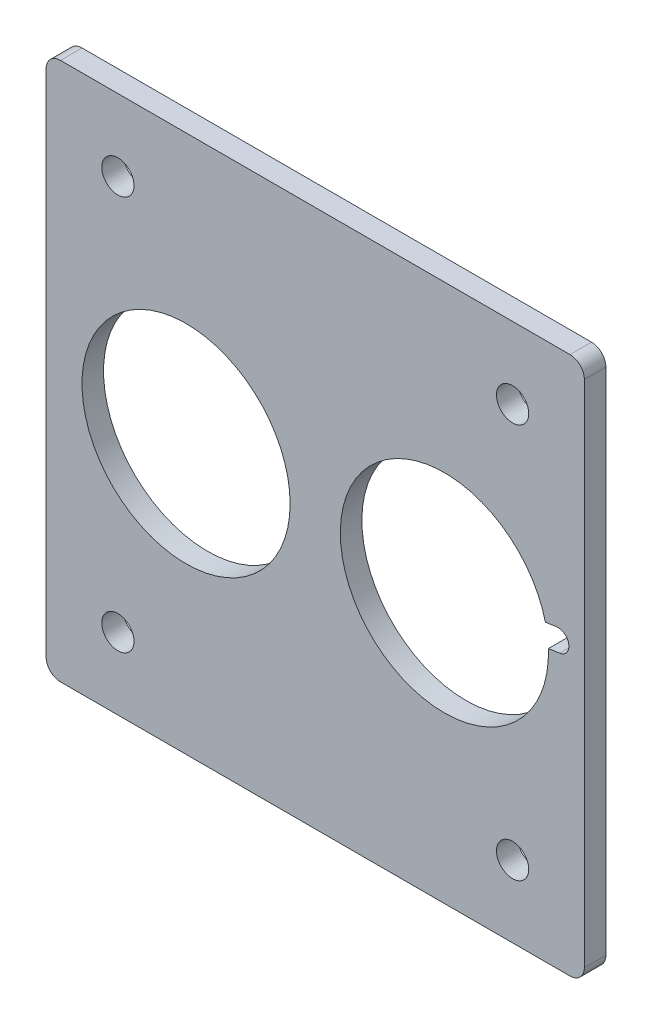
SolidWorks part; units mm, degrees
material "1.5714 (16NiCr4)"
ref_plane "Ebene vorne" through (0, 0, 0) normal (0, 0, 1) x (1, 0, 0)
ref_plane "Ebene oben" through (0, 0, 0) normal (0, 1, 0) x (1, 0, 0)
ref_plane "Ebene rechts" through (0, 0, 0) normal (1, 0, 0) x (0, 0, -1)
sketch "Skizze1" plane through (0, 0, 0) normal (0, 0, 1) x (1, 0, 0)
  line L1 (-37.5, -37.5) -> (37.5, -37.5)
  line L2 (-37.5, -37.5) -> (-37.5, 37.5)
  line L3 (-37.5, 37.5) -> (37.5, 37.5)
  line L4 (37.5, -37.5) -> (37.5, 37.5)
  line L5 (-37.5, -37.5) -> (37.5, 37.5) construction
  line L6 (-37.5, 37.5) -> (37.5, -37.5) construction
  point P0 (0, 0)
  dimension "D1" = 75
  dimension "D2" = 75
extrude "Aufsatz-Linear austragen1" add sketch "Skizze1" along normal blind 3
sketch "Skizze2" plane through (0, 0, 3) normal (0, 0, 1) x (1, 0, 0)
  line L0 (-18, 0) -> (18, 0) construction
  line L1 (18, 0) -> (37.5, 0) construction
  line L2 (37.5, -37.5) -> (37.5, 37.5) construction
  line L3 (-18, 0) -> (-37.5, 0) construction
  line L4 (-37.5, 37.5) -> (-37.5, -37.5) construction
  circle A0 centre (-18, 0) radius 14.5
  circle A1 centre (18, 0) radius 14.5
  dimension "D1" = 29
  dimension "D2" = 36
extrude "Schnitt-Linear austragen1" cut sketch "Skizze2" against normal through all
fillet "Verrundung1" radius 2 4 edges at (-37.5, -37.5, 1.5) (-37.5, 37.5, 1.5) (37.5, -37.5, 1.5) (37.5, 37.5, 1.5)
hole_wizard "Durchgangsloch für M41" positions "Skizze4" profile "Skizze5" hole size "M4" standard "ANSI Metrisch" end condition through all
sketch "Skizze4" plane through (0, 0, 3) normal (0, 0, 1) x (1, 0, 0)
  line L0 (-37.5, 27.5) -> (-27.5, 27.5) construction
  line L1 (-37.5, 35.5) -> (-37.5, -35.5) construction
  line L2 (-27.5, 27.5) -> (27.5, 27.5) construction
  line L3 (27.5, 27.5) -> (37.5, 27.5) construction
  line L4 (37.5, -35.5) -> (37.5, 35.5) construction
  line L5 (35.5, 37.5) -> (-35.5, 37.5) construction
  point P2 (-27.5, 27.5)
  point P6 (27.5, 27.5)
  dimension "D1" = 10
  dimension "D2" = 10
sketch "Skizze5" plane through (27.5, 27.5, 3) normal (1, 0, 0) x (0, -1, 0)
  line L0 (0, 0) -> (0, 3)
  line L1 (0, 3) -> (2.25, 3)
  line L2 (2.25, 3) -> (2.25, 0)
  line L5 (2.25, 0) -> (0, 0)
  line L11 (0, -6.35) -> (0, 107.95) construction
  dimension "Bohrerdurchmesser" = 4.5
  dimension "Bohrungstiefe" = 3
mirror "Spiegeln1" about plane through (0, 0, 0) normal (0, 1, 0) of "Durchgangsloch für M41"
sketch "Skizze6" plane through (0, 0, 3) normal (0, 0, 1) x (1, 0, 0)
  line L0 (32.3589, 2.018) -> (18, 0) construction
  line L1 (37.5, -35.5) -> (37.5, 35.5) construction
  line L2 (32.3589, 2.018) -> (37.5, 2.7405) construction
  line L3 (18, 0) -> (33.8443, 2.2268) construction
  line L4 (17.7912, 1.4854) -> (33.6355, 3.7122)
  line L5 (18.2088, -1.4854) -> (34.053, 0.7414)
  circle A0 centre (18, 0) radius 14.5 construction
  circle A1 centre (18, 0) radius 14.5 construction
  arc A3 (17.7912, 1.4854) -> (18.2088, -1.4854) centre (18, 0) ccw
  arc A4 (34.053, 0.7414) -> (33.6355, 3.7122) centre (33.8443, 2.2268) ccw
  circle A5 centre (33.8443, 2.2268) radius 1.5 construction
  point P9 (25.9221, 1.1134)
  dimension "D2" = 1.5
  dimension "D1" = 82
extrude "Schnitt-Linear austragen2" cut sketch "Skizze6" against normal through all contours L4 A4 L5 A3
